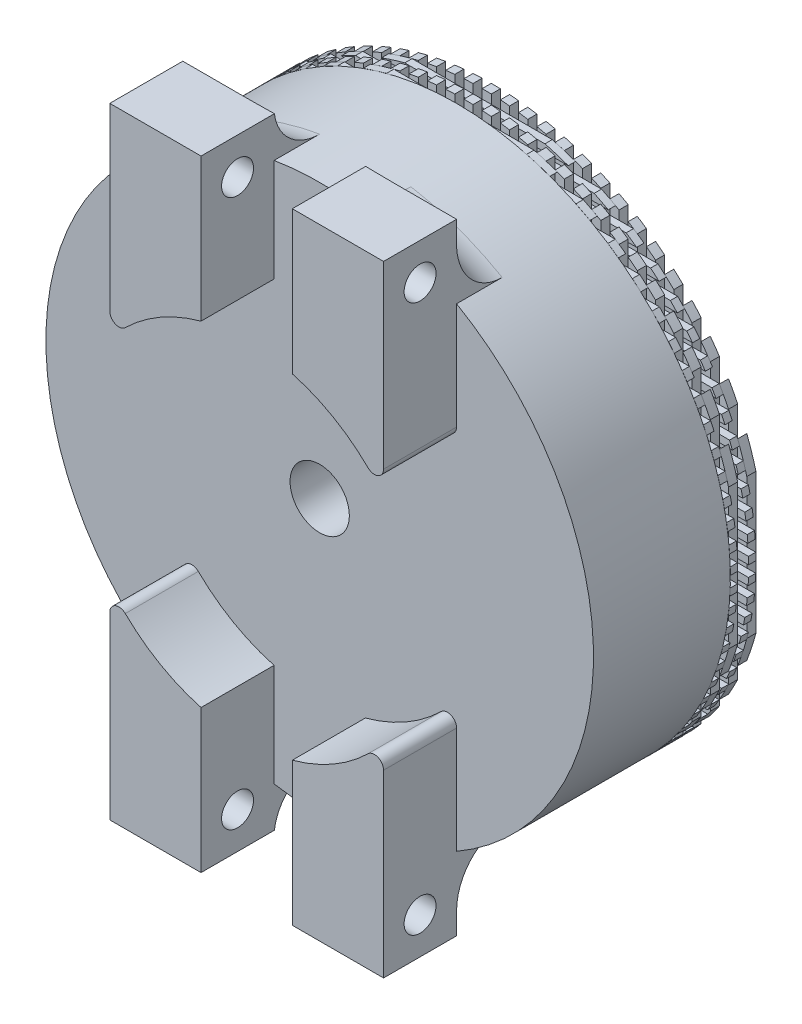
SolidWorks part; units mm, degrees
ref_plane "Front Plane" through (0, 0, 0) normal (1, 0, 0) x (0, 1, 0)
ref_plane "Top Plane" through (0, 0, 0) normal (0, 0, 1) x (0, 1, 0)
ref_plane "Right Plane" through (0, 0, 0) normal (0, 1, 0) x (-1, 0, 0)
sketch "Sketch1" plane through (0, 0, 0) normal (1, 0, 0) x (0, 1, 0)
  line L0 (64, -4) -> (68, -4) construction
  line L1 (0, 0) -> (68, 0)
  line L2 (0, 0) -> (0, -8)
  line L3 (0, -8) -> (68, -8)
  line L4 (68, 0) -> (68, -8)
  line L5 (4, -4) -> (0, -4) construction
  circle A0 centre (4, -4) radius 1.75
  circle A1 centre (64, -4) radius 1.75
  point P10 (0, -4)
  dimension "D1" = 3.5
  dimension "D2" = 60
  dimension "D3" = 8
  dimension "D4" = 4
extrude "Boss-Extrude1" add sketch "Sketch1" along normal blind 30
sketch "Sketch3" plane through (0, 0, -8) normal (0, 0, -1) x (1, 0, 0)
  line L1 (30, 0) -> (30, -68) construction
  line L2 (15, -34) -> (30, -34) construction
  line L3 (15, -34) -> (0, -34) construction
  line L4 (0, 0) -> (0, -68) construction
  circle A0 centre (15, -34) radius 30
  dimension "D1" = 60
extrude "Boss-Extrude2" add sketch "Sketch3" along normal blind 15
sketch "Sketch4" plane through (0, 0, 0) normal (0, 0, 1) x (1, 0, 0)
  circle A0 centre (15, 34) radius 19
  dimension "D1" = 38
extrude "Cut-Extrude1" cut sketch "Sketch4" against normal up to surface (8 mm away) and the other way through all up to face at (37.5, 34, -8)
ref_plane "Plane1" through (15, 0, 0) normal (1, 0, 0) x (0, 0, -1)
sketch "Sketch5" plane through (15, 0, 0) normal (1, 0, 0) x (0, 0, -1)
  line L0 (23, 4) -> (23, 64) construction
  line L1 (23, 63) -> (23.8, 63)
  line L2 (23, 63) -> (23, 62.2)
  line L3 (23, 62.2) -> (23.8, 62.2)
  line L4 (23.8, 63) -> (23.8, 62.2)
  line L5 (23, 64) -> (8, 64) construction
  line L6 (23, 61) -> (23, 60.2)
  line L7 (23, 61) -> (23.8, 61)
  line L8 (23.8, 61) -> (23.8, 60.2)
  line L9 (23, 60.2) -> (23.8, 60.2)
  line L10 (23, 59) -> (23, 58.2)
  line L11 (23, 59) -> (23.8, 59)
  line L12 (23.8, 59) -> (23.8, 58.2)
  line L13 (23, 58.2) -> (23.8, 58.2)
  line L14 (23, 57) -> (23, 56.2)
  line L15 (23, 57) -> (23.8, 57)
  line L16 (23.8, 57) -> (23.8, 56.2)
  line L17 (23, 56.2) -> (23.8, 56.2)
  line L18 (23, 55) -> (23, 54.2)
  line L19 (23, 55) -> (23.8, 55)
  line L20 (23.8, 55) -> (23.8, 54.2)
  line L21 (23, 54.2) -> (23.8, 54.2)
  line L22 (23, 53) -> (23, 52.2)
  line L23 (23, 53) -> (23.8, 53)
  line L24 (23.8, 53) -> (23.8, 52.2)
  line L25 (23, 52.2) -> (23.8, 52.2)
  line L26 (23, 51) -> (23, 50.2)
  line L27 (23, 51) -> (23.8, 51)
  line L28 (23.8, 51) -> (23.8, 50.2)
  line L29 (23, 50.2) -> (23.8, 50.2)
  line L30 (23, 49) -> (23, 48.2)
  line L31 (23, 49) -> (23.8, 49)
  line L32 (23.8, 49) -> (23.8, 48.2)
  line L33 (23, 48.2) -> (23.8, 48.2)
  line L34 (23, 47) -> (23, 46.2)
  line L35 (23, 47) -> (23.8, 47)
  line L36 (23.8, 47) -> (23.8, 46.2)
  line L37 (23, 46.2) -> (23.8, 46.2)
  line L38 (23, 45) -> (23, 44.2)
  line L39 (23, 45) -> (23.8, 45)
  line L40 (23.8, 45) -> (23.8, 44.2)
  line L41 (23, 44.2) -> (23.8, 44.2)
  line L42 (23, 43) -> (23, 42.2)
  line L43 (23, 43) -> (23.8, 43)
  line L44 (23.8, 43) -> (23.8, 42.2)
  line L45 (23, 42.2) -> (23.8, 42.2)
  line L46 (23, 41) -> (23, 40.2)
  line L47 (23, 41) -> (23.8, 41)
  line L48 (23.8, 41) -> (23.8, 40.2)
  line L49 (23, 40.2) -> (23.8, 40.2)
  line L50 (23, 39) -> (23, 38.2)
  line L51 (23, 39) -> (23.8, 39)
  line L52 (23.8, 39) -> (23.8, 38.2)
  line L53 (23, 38.2) -> (23.8, 38.2)
  line L54 (23, 37) -> (23, 36.2)
  line L55 (23, 37) -> (23.8, 37)
  line L56 (23.8, 37) -> (23.8, 36.2)
  line L57 (23, 36.2) -> (23.8, 36.2)
  line L58 (23, 35) -> (23, 34.2)
  line L59 (23, 35) -> (23.8, 35)
  line L60 (23.8, 35) -> (23.8, 34.2)
  line L61 (23, 34.2) -> (23.8, 34.2)
  line L62 (23, 33) -> (23, 32.2)
  line L63 (23, 33) -> (23.8, 33)
  line L64 (23.8, 33) -> (23.8, 32.2)
  line L65 (23, 32.2) -> (23.8, 32.2)
  line L66 (23, 31) -> (23, 30.2)
  line L67 (23, 31) -> (23.8, 31)
  line L68 (23.8, 31) -> (23.8, 30.2)
  line L69 (23, 30.2) -> (23.8, 30.2)
  line L70 (23, 29) -> (23, 28.2)
  line L71 (23, 29) -> (23.8, 29)
  line L72 (23.8, 29) -> (23.8, 28.2)
  line L73 (23, 28.2) -> (23.8, 28.2)
  line L74 (23, 27) -> (23, 26.2)
  line L75 (23, 27) -> (23.8, 27)
  line L76 (23.8, 27) -> (23.8, 26.2)
  line L77 (23, 26.2) -> (23.8, 26.2)
  line L78 (23, 25) -> (23, 24.2)
  line L79 (23, 25) -> (23.8, 25)
  line L80 (23.8, 25) -> (23.8, 24.2)
  line L81 (23, 24.2) -> (23.8, 24.2)
  line L82 (23, 23) -> (23, 22.2)
  line L83 (23, 23) -> (23.8, 23)
  line L84 (23.8, 23) -> (23.8, 22.2)
  line L85 (23, 22.2) -> (23.8, 22.2)
  line L86 (23, 21) -> (23, 20.2)
  line L87 (23, 21) -> (23.8, 21)
  line L88 (23.8, 21) -> (23.8, 20.2)
  line L89 (23, 20.2) -> (23.8, 20.2)
  line L90 (23, 19) -> (23, 18.2)
  line L91 (23, 19) -> (23.8, 19)
  line L92 (23.8, 19) -> (23.8, 18.2)
  line L93 (23, 18.2) -> (23.8, 18.2)
  line L94 (23, 17) -> (23, 16.2)
  line L95 (23, 17) -> (23.8, 17)
  line L96 (23.8, 17) -> (23.8, 16.2)
  line L97 (23, 16.2) -> (23.8, 16.2)
  line L98 (23, 15) -> (23, 14.2)
  line L99 (23, 15) -> (23.8, 15)
  line L100 (23.8, 15) -> (23.8, 14.2)
  line L101 (23, 14.2) -> (23.8, 14.2)
  line L102 (23, 13) -> (23, 12.2)
  line L103 (23, 13) -> (23.8, 13)
  line L104 (23.8, 13) -> (23.8, 12.2)
  line L105 (23, 12.2) -> (23.8, 12.2)
  line L106 (23, 11) -> (23, 10.2)
  line L107 (23, 11) -> (23.8, 11)
  line L108 (23.8, 11) -> (23.8, 10.2)
  line L109 (23, 10.2) -> (23.8, 10.2)
  line L110 (23, 9) -> (23, 8.2)
  line L111 (23, 9) -> (23.8, 9)
  line L112 (23.8, 9) -> (23.8, 8.2)
  line L113 (23, 8.2) -> (23.8, 8.2)
  line L114 (23, 7) -> (23, 6.2)
  line L115 (23, 7) -> (23.8, 7)
  line L116 (23.8, 7) -> (23.8, 6.2)
  line L117 (23, 6.2) -> (23.8, 6.2)
  line L118 (23, 5) -> (23, 4.2)
  line L119 (23, 5) -> (23.8, 5)
  line L120 (23.8, 5) -> (23.8, 4.2)
  line L121 (23, 4.2) -> (23.8, 4.2)
  line L122 (23, 3) -> (23, 2.2)
  line L123 (23, 3) -> (23.8, 3)
  line L124 (23.8, 3) -> (23.8, 2.2)
  line L125 (23, 2.2) -> (23.8, 2.2)
  line L126 (23, 63) -> (23, 61) construction
  dimension "D1" = 0.8
  dimension "D2" = 1
  dimension "D4" = 2
  dimension "D3" = 31
extrude "Boss-Extrude3" add sketch "Sketch5" along normal mid plane 75 separate body
ref_plane "Plane2" through (0, 34, 0) normal (0, -1, 0) x (-1, 0, 0)
sketch "Sketch6" plane through (0, 34, 0) normal (0, -1, 0) x (-1, 0, 0)
  line L0 (-52.5, 23.8) -> (22.5, 23.8) construction
  line L1 (-44, 23.8) -> (-43, 23.8)
  line L2 (-44, 23.8) -> (-44, 24.8)
  line L3 (-44, 24.8) -> (-43, 24.8)
  line L4 (-43, 23.8) -> (-43, 24.8)
  line L5 (-45, 23) -> (-45, 8) construction
  line L6 (-42, 23.8) -> (-42, 24.8)
  line L7 (-42, 23.8) -> (-41, 23.8)
  line L8 (-41, 23.8) -> (-41, 24.8)
  line L9 (-42, 24.8) -> (-41, 24.8)
  line L10 (-40, 23.8) -> (-40, 24.8)
  line L11 (-40, 23.8) -> (-39, 23.8)
  line L12 (-39, 23.8) -> (-39, 24.8)
  line L13 (-40, 24.8) -> (-39, 24.8)
  line L14 (-38, 23.8) -> (-38, 24.8)
  line L15 (-38, 23.8) -> (-37, 23.8)
  line L16 (-37, 23.8) -> (-37, 24.8)
  line L17 (-38, 24.8) -> (-37, 24.8)
  line L18 (-36, 23.8) -> (-36, 24.8)
  line L19 (-36, 23.8) -> (-35, 23.8)
  line L20 (-35, 23.8) -> (-35, 24.8)
  line L21 (-36, 24.8) -> (-35, 24.8)
  line L22 (-34, 23.8) -> (-34, 24.8)
  line L23 (-34, 23.8) -> (-33, 23.8)
  line L24 (-33, 23.8) -> (-33, 24.8)
  line L25 (-34, 24.8) -> (-33, 24.8)
  line L26 (-32, 23.8) -> (-32, 24.8)
  line L27 (-32, 23.8) -> (-31, 23.8)
  line L28 (-31, 23.8) -> (-31, 24.8)
  line L29 (-32, 24.8) -> (-31, 24.8)
  line L30 (-30, 23.8) -> (-30, 24.8)
  line L31 (-30, 23.8) -> (-29, 23.8)
  line L32 (-29, 23.8) -> (-29, 24.8)
  line L33 (-30, 24.8) -> (-29, 24.8)
  line L34 (-28, 23.8) -> (-28, 24.8)
  line L35 (-28, 23.8) -> (-27, 23.8)
  line L36 (-27, 23.8) -> (-27, 24.8)
  line L37 (-28, 24.8) -> (-27, 24.8)
  line L38 (-26, 23.8) -> (-26, 24.8)
  line L39 (-26, 23.8) -> (-25, 23.8)
  line L40 (-25, 23.8) -> (-25, 24.8)
  line L41 (-26, 24.8) -> (-25, 24.8)
  line L42 (-24, 23.8) -> (-24, 24.8)
  line L43 (-24, 23.8) -> (-23, 23.8)
  line L44 (-23, 23.8) -> (-23, 24.8)
  line L45 (-24, 24.8) -> (-23, 24.8)
  line L46 (-22, 23.8) -> (-22, 24.8)
  line L47 (-22, 23.8) -> (-21, 23.8)
  line L48 (-21, 23.8) -> (-21, 24.8)
  line L49 (-22, 24.8) -> (-21, 24.8)
  line L50 (-20, 23.8) -> (-20, 24.8)
  line L51 (-20, 23.8) -> (-19, 23.8)
  line L52 (-19, 23.8) -> (-19, 24.8)
  line L53 (-20, 24.8) -> (-19, 24.8)
  line L54 (-18, 23.8) -> (-18, 24.8)
  line L55 (-18, 23.8) -> (-17, 23.8)
  line L56 (-17, 23.8) -> (-17, 24.8)
  line L57 (-18, 24.8) -> (-17, 24.8)
  line L58 (-16, 23.8) -> (-16, 24.8)
  line L59 (-16, 23.8) -> (-15, 23.8)
  line L60 (-15, 23.8) -> (-15, 24.8)
  line L61 (-16, 24.8) -> (-15, 24.8)
  line L62 (-14, 23.8) -> (-14, 24.8)
  line L63 (-14, 23.8) -> (-13, 23.8)
  line L64 (-13, 23.8) -> (-13, 24.8)
  line L65 (-14, 24.8) -> (-13, 24.8)
  line L66 (-12, 23.8) -> (-12, 24.8)
  line L67 (-12, 23.8) -> (-11, 23.8)
  line L68 (-11, 23.8) -> (-11, 24.8)
  line L69 (-12, 24.8) -> (-11, 24.8)
  line L70 (-10, 23.8) -> (-10, 24.8)
  line L71 (-10, 23.8) -> (-9, 23.8)
  line L72 (-9, 23.8) -> (-9, 24.8)
  line L73 (-10, 24.8) -> (-9, 24.8)
  line L74 (-8, 23.8) -> (-8, 24.8)
  line L75 (-8, 23.8) -> (-7, 23.8)
  line L76 (-7, 23.8) -> (-7, 24.8)
  line L77 (-8, 24.8) -> (-7, 24.8)
  line L78 (-6, 23.8) -> (-6, 24.8)
  line L79 (-6, 23.8) -> (-5, 23.8)
  line L80 (-5, 23.8) -> (-5, 24.8)
  line L81 (-6, 24.8) -> (-5, 24.8)
  line L82 (-4, 23.8) -> (-4, 24.8)
  line L83 (-4, 23.8) -> (-3, 23.8)
  line L84 (-3, 23.8) -> (-3, 24.8)
  line L85 (-4, 24.8) -> (-3, 24.8)
  line L86 (-2, 23.8) -> (-2, 24.8)
  line L87 (-2, 23.8) -> (-1, 23.8)
  line L88 (-1, 23.8) -> (-1, 24.8)
  line L89 (-2, 24.8) -> (-1, 24.8)
  line L90 (0, 23.8) -> (0, 24.8)
  line L91 (0, 23.8) -> (1, 23.8)
  line L92 (1, 23.8) -> (1, 24.8)
  line L93 (0, 24.8) -> (1, 24.8)
  line L94 (2, 23.8) -> (2, 24.8)
  line L95 (2, 23.8) -> (3, 23.8)
  line L96 (3, 23.8) -> (3, 24.8)
  line L97 (2, 24.8) -> (3, 24.8)
  line L98 (4, 23.8) -> (4, 24.8)
  line L99 (4, 23.8) -> (5, 23.8)
  line L100 (5, 23.8) -> (5, 24.8)
  line L101 (4, 24.8) -> (5, 24.8)
  line L102 (6, 23.8) -> (6, 24.8)
  line L103 (6, 23.8) -> (7, 23.8)
  line L104 (7, 23.8) -> (7, 24.8)
  line L105 (6, 24.8) -> (7, 24.8)
  line L106 (8, 23.8) -> (8, 24.8)
  line L107 (8, 23.8) -> (9, 23.8)
  line L108 (9, 23.8) -> (9, 24.8)
  line L109 (8, 24.8) -> (9, 24.8)
  line L110 (10, 23.8) -> (10, 24.8)
  line L111 (10, 23.8) -> (11, 23.8)
  line L112 (11, 23.8) -> (11, 24.8)
  line L113 (10, 24.8) -> (11, 24.8)
  line L114 (12, 23.8) -> (12, 24.8)
  line L115 (12, 23.8) -> (13, 23.8)
  line L116 (13, 23.8) -> (13, 24.8)
  line L117 (12, 24.8) -> (13, 24.8)
  line L118 (14, 23.8) -> (14, 24.8)
  line L119 (14, 23.8) -> (15, 23.8)
  line L120 (15, 23.8) -> (15, 24.8)
  line L121 (14, 24.8) -> (15, 24.8)
  line L122 (16, 23.8) -> (16, 24.8)
  line L123 (16, 23.8) -> (17, 23.8)
  line L124 (17, 23.8) -> (17, 24.8)
  line L125 (16, 24.8) -> (17, 24.8)
  line L126 (-44, 23.8) -> (-42, 23.8) construction
  dimension "D1" = 1
  dimension "D2" = 1
  dimension "D4" = 2
  dimension "D3" = 31
extrude "Boss-Extrude4" add sketch "Sketch6" along normal mid plane 74 separate body
pattern_linear "LPattern1" count 2 spacing 2 along (0, 0, -1) of "Boss-Extrude3", "Boss-Extrude4"
sketch "Sketch7" plane through (0, 0, -8) normal (0, 0, -1) x (1, 0, 0)
  circle A0 centre (15, -34) radius 30
  circle A4 centre (15, -34) radius 30 construction
  circle A5 centre (15, -34) radius 72.5485
  dimension "D1" = 60
extrude "Cut-Extrude2" cut sketch "Sketch7" along normal through all contours A5 A0 region at (-55.4965, 34, -8)
fillet "Fillet3" radius 1 4 edges at (30, 22.3381, -4) (30, 45.6619, -4) (0, 45.6619, -4) (0, 22.3381, -4)
sketch "Sketch8" plane through (0, 0, 0) normal (0, 0, 1) x (1, 0, 0)
  line L0 (20, 34) -> (15, 34) construction
  line L1 (10, 71.5) -> (20, 71.5)
  line L2 (10, 71.5) -> (10, -3.5)
  line L3 (10, -3.5) -> (20, -3.5)
  line L4 (20, 71.5) -> (20, -3.5)
  line L5 (15, -13.3161) -> (15, 13.3161) construction
  line L6 (15, 34) -> (10, 34) construction
  line L7 (-10.9219, 34) -> (10.9219, 34) construction
  dimension "D1" = 10
  dimension "D2" = 75
extrude "Cut-Extrude3" cut sketch "Sketch8" against normal up to surface (8 mm away) up to face at (15, 34, -8)
fillet "Fillet1" radius 5 4 edges at (25.1607, 5.7731, -8) (4.8393, 5.7731, -8) (4.8393, 62.2269, -8) (25.1607, 62.2269, -8)
sketch "Sketch9" plane through (0, 0, -8) normal (0, 0, 1) x (1, 0, 0)
  circle A0 centre (15, 34) radius 3.25
  dimension "D1" = 6.5
extrude "Cut-Extrude4" cut sketch "Sketch9" against normal up to surface (15 mm away) up to face at (15, 64, -23)
sketch "Sketch10" plane through (0, 0, -23) normal (0, 0, -1) x (-1, 0, 0)
  line L0 (-15, 34) -> (-45, 34) construction
  circle A0 centre (-23, 34) radius 1.25
  circle A1 centre (-19, 40.9282) radius 1.25
  circle A2 centre (-15, 34) radius 8 construction
  circle A3 centre (-15, 34) radius 3.25 construction
  circle A4 centre (-15, 34) radius 30 construction
  circle A5 centre (-27, 34) radius 1.25
  circle A6 centre (-32, 34) radius 1.25
  circle A7 centre (-38, 34) radius 1.25
  circle A8 centre (-21, 44.3923) radius 1.25
  circle A9 centre (-23.5, 48.7224) radius 1.25
  circle A10 centre (-26.5, 53.9186) radius 1.25
  circle A11 centre (-11, 40.9282) radius 1.25
  circle A12 centre (-9, 44.3923) radius 1.25
  circle A13 centre (-6.5, 48.7224) radius 1.25
  circle A14 centre (-3.5, 53.9186) radius 1.25
  circle A15 centre (-7, 34) radius 1.25
  circle A16 centre (-3, 34) radius 1.25
  circle A17 centre (2, 34) radius 1.25
  circle A18 centre (8, 34) radius 1.25
  circle A19 centre (-11, 27.0718) radius 1.25
  circle A20 centre (-9, 23.6077) radius 1.25
  circle A21 centre (-6.5, 19.2776) radius 1.25
  circle A22 centre (-3.5, 14.0814) radius 1.25
  circle A23 centre (-19, 27.0718) radius 1.25
  circle A24 centre (-21, 23.6077) radius 1.25
  circle A25 centre (-23.5, 19.2776) radius 1.25
  circle A26 centre (-26.5, 14.0814) radius 1.25
  dimension "D1" = 2.5
  dimension "D2" = 16
  dimension "D3" = 4
  dimension "D4" = 5
  dimension "D5" = 6
  dimension "D6" = 6
extrude "Cut-Extrude5" cut sketch "Sketch10" against normal blind 10 draft 5 draft outward yes
